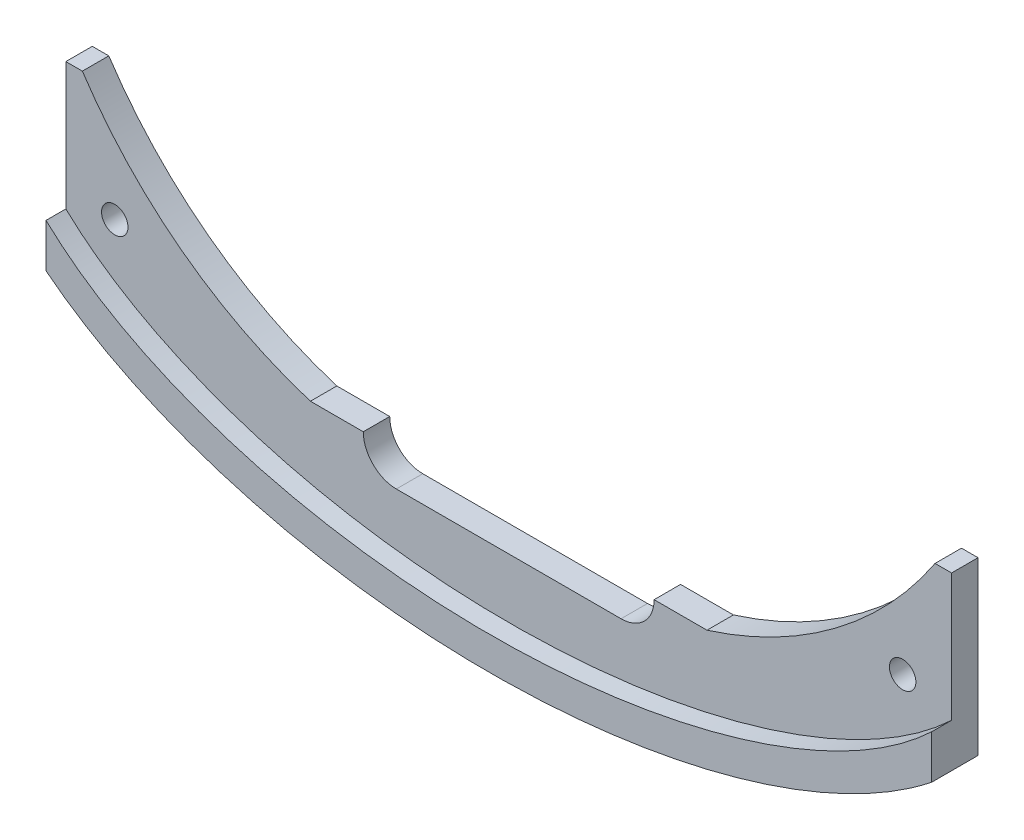
SolidWorks part; units mm, degrees
ref_plane "Alzado" through (0, 0, 0) normal (0, 0, 1) x (1, 0, 0)
ref_plane "Planta" through (0, 0, 0) normal (0, 1, 0) x (1, 0, 0)
ref_plane "Vista lateral" through (0, 0, 0) normal (1, 0, 0) x (0, 0, -1)
sketch "Croquis1" plane through (0, 0, 0) normal (0, 0, 1) x (1, 0, 0)
  line L0 (0, 14) -> (30, 14)
  line L3 (-76.5, 40) -> (-64.5, 40)
  line L5 (0, 14) -> (-30, 14)
  line L6 (0, 0) -> (0, 40) construction
  line L7 (64.5, 40) -> (76.5, 40)
  line L8 (-59.6, 23) -> (59.6, 23) construction
  circle A0 centre (7.25, 8) radius 2
  circle A1 centre (59.6, 23) radius 2
  circle A2 centre (-7.25, 8) radius 2
  circle A3 centre (-59.6, 23) radius 2
  arc A6 (-30, 14) -> (-64.5, 40) centre (-10.6545, 75.5595) cw
  arc A7 (30, 14) -> (64.5, 40) centre (10.6545, 75.5595) ccw
  ellipse E0 centre (0, 40) end of major axis (76.5, 40) minor radius 40 (-76.5, 40) -> (76.5, 40) ccw
  dimension "D3" = 4
  dimension "D5" = 4
  dimension "D10" = 8
  dimension "D2" = 153
  dimension "D4" = 30
  dimension "D6" = 119.2
  dimension "D7" = 15
  dimension "D8" = 40
  dimension "D9" = 12
  dimension "D11" = 14.5
  dimension "D12" = 14
extrude "Saliente-Extruir1" add sketch "Croquis1" along normal blind 4
ref_plane "Plano1" through (0, 0, -3) normal (0, 0, -1) x (-1, 0, 0)
sketch "Croquis2" plane through (0, 0, -3) normal (0, 0, -1) x (-1, 0, 0)
  line L3 (0, 0) -> (0, 33.4572) construction
  line L6 (64.5, 40) -> (76.5, 40) construction
  line L7 (-30, 14) -> (30, 14) construction
  line L8 (-76.5, 40) -> (-64.5, 40) construction
  line L9 (64.5, 40) -> (76.5, 40)
  line L10 (-30, 14) -> (30, 14)
  line L11 (-76.5, 40) -> (-64.5, 40)
  arc A8 (30, 14) -> (64.5, 40) centre (10.6545, 75.5595) ccw construction
  circle A10 centre (-59.6, 23) radius 2 construction
  circle A12 centre (7.25, 8) radius 2 construction
  circle A13 centre (-7.25, 8) radius 2 construction
  arc A14 (-64.5, 40) -> (-30, 14) centre (-10.6545, 75.5595) ccw construction
  arc A15 (30, 14) -> (64.5, 40) centre (10.6545, 75.5595) ccw
  circle A17 centre (-59.6, 23) radius 2
  circle A19 centre (7.25, 8) radius 2
  circle A20 centre (-7.25, 8) radius 2
  arc A21 (-64.5, 40) -> (-30, 14) centre (-10.6545, 75.5595) ccw
  circle A22 centre (59.6, 23) radius 2 construction
  circle A23 centre (59.6, 23) radius 2
  ellipse E0 centre (0, 40) end of major axis (-76.5, 40) minor radius 40 (-76.5, 40) -> (76.5, 40) ccw construction
  ellipse E1 centre (0, 40) end of major axis (-76.5, 40) minor radius 40 (-76.5, 40) -> (76.5, 40) ccw
extrude "Saliente-Extruir2" add sketch "Croquis2" along normal blind 4 separate body
ref_plane "Plano2" through (0, 0, 4) normal (0, 0, 1) x (1, 0, 0)
sketch "Croquis3" plane through (0, 0, 4) normal (0, 0, 1) x (1, 0, 0)
  line L2 (-81.5, 40) -> (-76.5, 40)
  line L3 (81.5, 40) -> (76.5, 40)
  ellipse E1 centre (0, 40) end of major axis (76.5, 40) minor radius 40 (-76.5, 40) -> (76.5, 40) ccw construction
  ellipse E2 centre (0, 40) end of major axis (76.5, 40) minor radius 40 (-76.5, 40) -> (76.5, 40) ccw
  spline S0 degree 1 poles (-81.5, 40) (81.5, 40) knots 0 0 1 1 construction
  spline S1 degree 3 poles (-81.5, 40) (-81.5, 36.7505) (-80.261, 30.281) (-73.3217, 18.4428) (-57.7398, 6.4288) (-31.0655, -2.8514) (0, -6.0743) (31.0655, -2.8514) (57.7398, 6.4288) (73.3217, 18.4428) (80.261, 30.281) (81.5, 36.7505) (81.5, 40) knots 3.141593 3.141593 3.141593 3.141593 3.337942 3.534292 3.926991 4.31969 4.712389 5.105088 5.497787 5.890486 6.086836 6.283185 6.283185 6.283185 6.283185
  dimension "D1" = 5
extrude "Saliente-Extruir3" add sketch "Croquis3" against normal up to surface (11 mm away) contours L3 E2 L2 S1 up to face at (5.25, 8, -7)
sketch "Croquis4" plane through (0, 0, 0) normal (0, 0, 1) x (1, 0, 0)
  line L0 (30, 14) -> (-30, 14) construction
  line L1 (30, 14) -> (-30, 14)
  line L2 (-39.8217, 18) -> (39.8217, 18)
  arc A0 (-64.5, 40) -> (-30, 14) centre (-10.6545, 75.5595) ccw construction
  arc A1 (30, 14) -> (64.5, 40) centre (10.6545, 75.5595) ccw construction
  arc A2 (-39.8217, 18) -> (-30, 14) centre (-10.6545, 75.5595) ccw
  arc A3 (30, 14) -> (39.8217, 18) centre (10.6545, 75.5595) ccw
  dimension "D1" = 4
extrude "Saliente-Extruir4" add sketch "Croquis4" along normal blind 4
sketch "Croquis5" plane through (0, 0, 4) normal (0, 0, 1) x (1, 0, 0)
  line L0 (39.8217, 18) -> (-39.8217, 18) construction
  line L1 (40.755, 18) -> (-40.755, 18)
  line L2 (40.755, 18) -> (40.755, 14)
  line L3 (40.755, 14) -> (-40.755, 14)
  line L4 (-40.755, 18) -> (-40.755, 14)
  point P6 (0, 14)
  dimension "D1" = 4
  dimension "D2" = 81.51
extrude "Saliente-Extruir5" add sketch "Croquis5" along normal blind 45 contours L2 L1 L4 L3
sketch "Croquis6" plane through (0, 14, 0) normal (0, -1, 0) x (-1, 0, 0)
  line L0 (13.075, -29) -> (-13.075, -29) construction
  line L1 (40.755, -4) -> (-40.755, -4) construction
  line L2 (0, -4) -> (0, -39) construction
  line L3 (35.826, -4) -> (35.826, -49) construction
  line L4 (-40.755, -4) -> (40.755, -4) construction
  line L5 (-40.755, -49) -> (40.755, -49) construction
  circle A0 centre (13.075, -29) radius 8.15
  circle A1 centre (-13.075, -29) radius 8.125
  circle A2 centre (35.826, -43.4034) radius 2.65
  circle A3 centre (35.826, -33.4034) radius 2.65
  circle A4 centre (-35.826, -33.4034) radius 2.65
  circle A5 centre (-35.826, -43.4034) radius 2.65
  point P18 (0, -29)
  dimension "D2" = 16.3
  dimension "D3" = 16.25
  dimension "D6" = 5.3
  dimension "D7" = 5.3
  dimension "D4" = 26.15
  dimension "D1" = 25
  dimension "D8" = 10
extrude "Cortar-Extruir1" cut sketch "Croquis6" against normal blind 25 contours A2 | A3 | A0 | A1 | A5 | A4
ref_plane "Plano4" through (0, -1, 0) normal (0, 1, 0) x (1, 0, 0)
sketch "Croquis7" plane through (0, -1, 0) normal (0, 1, 0) x (1, 0, 0)
  line L0 (0, -9.7855) -> (0, 13.9568) construction
  line L1 (-81.5, -4) -> (81.5, -4) construction
  line L2 (-55, -4) -> (-45, -4)
  line L3 (-55, -4) -> (-55, 7)
  line L4 (-55, 7) -> (-45, 7)
  line L5 (-45, -4) -> (-45, 7)
  line L6 (81.5, 7) -> (-81.5, 7) construction
  line L7 (55, 7) -> (45, 7)
  line L8 (55, -4) -> (55, 7)
  line L9 (55, -4) -> (45, -4)
  line L10 (45, -4) -> (45, 7)
  dimension "D1" = 10
  dimension "D2" = 55
extrude "Saliente-Extruir6" [suppressed] add sketch "Croquis7" along normal up to surface and the other way blind 6.08
sketch "Croquis16" [suppressed] plane through (0, -9.08, 0) normal (0, -1, 0) x (1, 0, 0)
  line L8 (-50, -6.5) -> (-50, 4.3) construction
  line L9 (-55, -1.1) -> (-45, -1.1) construction
  line L18 (50, 4.3) -> (50, -6.5) construction
  line L19 (45, -1.1) -> (55, -1.1) construction
  circle A0 centre (-50, -1.1) radius 4
  circle A1 centre (50, -1.1) radius 4
  dimension "D1" = 8
  dimension "D2" = 8
extrude "Cortar-Extruir6" [suppressed] cut sketch "Croquis16" against normal blind 16.3
sketch "Croquis17" plane through (0, 14, 0) normal (0, -1, 0) x (1, 0, 0)
  line L0 (-20.0239, 37.988) -> (-14.3005, 42.0182) construction
  line L1 (-20.5996, 38.8056) -> (-14.8763, 42.8359)
  line L2 (-19.4481, 37.1703) -> (-13.7248, 41.2006)
  line L3 (14.2242, 42.0182) -> (19.9475, 37.988) construction
  line L4 (14.7999, 42.8359) -> (20.5233, 38.8056)
  line L5 (13.6484, 41.2006) -> (19.3718, 37.1703)
  line L7 (-0.0382, 31.8728) -> (-0.0382, 6.8728) construction
  line L8 (-14.3005, 42.0182) -> (14.2242, 42.0182) construction
  line L9 (-20.0239, 37.988) -> (19.9475, 37.988) construction
  arc A0 (-20.5996, 38.8056) -> (-19.4481, 37.1703) centre (-20.0239, 37.988) ccw
  arc A1 (-13.7248, 41.2006) -> (-14.8763, 42.8359) centre (-14.3005, 42.0182) ccw
  arc A2 (14.7999, 42.8359) -> (13.6484, 41.2006) centre (14.2242, 42.0182) ccw
  arc A3 (19.3718, 37.1703) -> (20.5233, 38.8056) centre (19.9475, 37.988) ccw
  arc A4 (-20.8514, 31.4391) -> (-21.2225, 29.203) centre (-13.075, 29) ccw
  arc A6 (-10.8066, 17.5553) -> (11.1701, 17.5553) centre (0.1818, 45.4654) ccw
  arc A7 (-11.1729, 16.6248) -> (11.5364, 16.6248) centre (0.1818, 45.4654) ccw
  arc A8 (-10.8066, 17.5553) -> (-11.1729, 16.6248) centre (-10.9898, 17.09) ccw
  arc A9 (11.5364, 16.6248) -> (11.1701, 17.5553) centre (11.3533, 17.09) ccw
  circle A10 centre (-13.075, 29) radius 8.15 construction
  arc A13 (20.7751, 31.4391) -> (21.1461, 29.203) centre (12.9987, 29) cw
  ellipse E0 centre (-0.0382, 20.6274) end of major axis (3.8018, 20.6274) minor radius 1.3066
  spline S0 degree 2 poles (-20.8514, 31.4391) (-23.6077, 31.2523) (-25.4765, 33.8858) knots 0 0 0 1 1 1
  spline S1 degree 3 poles (-25.4765, 33.8858) (-24.9367, 29.7669) (-23.9591, 29.7982) (-21.2225, 29.203) knots 0 0 0 0 0.707855 0.707855 0.707855 0.707855
  spline S2 degree 3 poles (25.4002, 33.8858) (24.8603, 29.7669) (23.8827, 29.7982) (21.1461, 29.203) knots 0 0 0 0 0.707855 0.707855 0.707855 0.707855
  spline S3 degree 2 poles (20.7751, 31.4391) (23.5313, 31.2523) (25.4002, 33.8858) knots 0 0 0 1 1 1
  point P2 (-17.1622, 40.0031)
  point P7 (17.0859, 40.0031)
  point P54 (-0.0382, 37.988)
  dimension "D2" = 1
  dimension "D1" = 7
extrude "Saliente-Extruir9" add sketch "Croquis17" along normal blind 2
sketch "Croquis18" [suppressed] plane through (0, 0, -6.6) normal (0, 0, -1) x (-1, 0, 0)
  line L0 (0, 12) -> (0, -15.2947) construction
  line L1 (30, 12) -> (-30, 12) construction
  line L2 (50, 2.42) -> (50, -5.58) construction
  line L3 (51.5, 2.42) -> (51.5, -5.58)
  line L4 (48.5, 2.42) -> (48.5, -5.58)
  line L5 (55, -9.08) -> (55, 5.7348) construction
  line L6 (45, -9.08) -> (45, 1.7946) construction
  line L7 (-50, 2.42) -> (-50, -5.58) construction
  line L8 (-51.5, 2.42) -> (-51.5, -5.58)
  line L9 (-48.5, 2.42) -> (-48.5, -5.58)
  line L10 (45, -9.08) -> (55, -9.08) construction
  arc A0 (51.5, 2.42) -> (48.5, 2.42) centre (50, 2.42) ccw
  arc A1 (48.5, -5.58) -> (51.5, -5.58) centre (50, -5.58) ccw
  arc A2 (-51.5, 2.42) -> (-48.5, 2.42) centre (-50, 2.42) cw
  arc A3 (-48.5, -5.58) -> (-51.5, -5.58) centre (-50, -5.58) cw
  point P7 (50, -1.58)
  point P18 (-50, -1.58)
  dimension "D2" = 1.5
  dimension "D1" = 8
  dimension "D3" = 3.5
extrude "Cortar-Extruir7" [suppressed] cut sketch "Croquis18" against normal through all
sketch "Croquis19" [suppressed] plane through (0, 0, -3) normal (0, 0, 1) x (1, 0, 0)
  line L0 (0, 0) -> (0, 34.2296) construction
  line L2 (-64.5, 40) -> (-81.5, 40) construction
  circle A0 centre (0, -2.5) radius 0.75
  circle A1 centre (-79, 36.5) radius 0.75
  circle A2 centre (79, 36.5) radius 0.75
  dimension "D1" = 1.5
  dimension "D2" = 1.5
  dimension "D4" = 2.5
  dimension "D3" = 2.5
  dimension "D5" = 3.5
sketch "Croquis20" plane through (0, 0, 0) normal (1, 0, 0) x (0, 0, -1)
  line L0 (0, 40) -> (0, -5)
  line L1 (-4, -5) -> (7, -5) construction
  line L2 (0, -5) -> (-49.6594, -5)
  line L3 (-49.6594, -5) -> (-49.6594, 40)
  line L4 (-49.6594, 40) -> (0, 40)
extrude "Cortar-Extruir9" cut sketch "Croquis20" against normal through all both and the other way through all
sketch "Croquis21" plane through (0, 0, -7) normal (0, 0, -1) x (-1, 0, 0)
  circle A0 centre (-7.25, 8) radius 2 construction
  circle A1 centre (7.25, 8) radius 2 construction
  circle A2 centre (-7.25, 8) radius 2
  circle A3 centre (7.25, 8) radius 2
extrude "Saliente-Extruir11" add sketch "Croquis21" against normal up to surface (4 mm away) up to face at (0, 23.6757, -3)
sketch "Croquis22" plane through (0, 0, -7) normal (0, 0, -1) x (-1, 0, 0)
  line L0 (67, 40) -> (67, 14.0793)
  line L2 (-67, 40) -> (-67, 14.0793)
  line L4 (67, 14.0793) -> (95.2028, 14.0793)
  line L5 (67, 14.0793) -> (67, 40)
  line L6 (67, 40) -> (95.2028, 40)
  line L7 (95.2028, 14.0793) -> (95.2028, 40)
  line L8 (-67, 14.0793) -> (-97.8279, 14.0793)
  line L9 (-67, 14.0793) -> (-67, 40)
  line L10 (-67, 40) -> (-97.8279, 40)
  line L11 (-97.8279, 14.0793) -> (-97.8279, 40)
  spline S1 degree 3 poles (81.5, 40) (81.5, 36.7505) (80.261, 30.281) (73.3217, 18.4428) (57.7398, 6.4288) (31.0655, -2.8514) (0, -6.0743) (-31.0655, -2.8514) (-57.7398, 6.4288) (-73.3217, 18.4428) (-80.261, 30.281) (-81.5, 36.7505) (-81.5, 40) knots 3.141593 3.141593 3.141593 3.141593 3.337942 3.534292 3.926991 4.31969 4.712389 5.105088 5.497787 5.890486 6.086836 6.283185 6.283185 6.283185 6.283185 construction
  spline M3 degree 3 poles (-81.5, 40) (-81.5, 36.7505) (-80.261, 30.281) (-73.3217, 18.4428) (-57.7398, 6.4288) (-31.0655, -2.8514) (0, -6.0743) (31.0655, -2.8514) (57.7398, 6.4288) (73.3217, 18.4428) (80.261, 30.281) (81.5, 36.7505) (81.5, 40) knots 3.141593 3.141593 3.141593 3.141593 3.337942 3.534292 3.926991 4.31969 4.712389 5.105088 5.497787 5.890486 6.086836 6.283185 6.283185 6.283185 6.283185
  line M4 (81.5, 40) -> (64.5, 40)
  line M8 (-64.5, 40) -> (-81.5, 40)
  dimension "D1" = 134
  dimension "D2" = 67
extrude "Cortar-Extruir10" cut sketch "Croquis22" against normal blind 10 contours L4 L7 L6 M3 | L2 M8 M3 | L11 L8 L10 M3 | L0 M4 M3 region at (-72.8551, 30.1323, -7) region at (86.9254, 25.58, -7) region at (72.8551, 30.1323, -7) region at (-85.5511, 25.3709, -7)
sketch "Croquis23" plane through (0, 0, 0) normal (1, 0, 0) x (0, 0, -1)
  line L0 (7, 14) -> (7, -6.3364)
  line L1 (7, 14) -> (9, 14)
  line L2 (9, 14) -> (9, 13)
  line L3 (9, 13) -> (8, 13)
  line L4 (8, 13) -> (8, 8)
  line L5 (8, 8) -> (11, 8)
  line L6 (11, 8) -> (11, 10)
  line L7 (11, 10) -> (13, 10)
  line L8 (13, 10) -> (13, 6)
  line L9 (13, 6) -> (7, 6)
  line L10 (7, 21) -> (7, 25) construction
  dimension "D1" = 2
  dimension "D2" = 1
  dimension "D3" = 5
  dimension "D4" = 3
  dimension "D5" = 2
  dimension "D6" = 2
  dimension "D7" = 2
  dimension "D8" = 1
extrude "Saliente-Extruir12" [suppressed] add sketch "Croquis23" along normal blind 13 and the other way blind 13 contours L9 L8 L7 L6 L5 L4 L3 L2 L1 L0
sketch "Croquis24" plane through (0, 0, -7) normal (0, 0, -1) x (-1, 0, 0)
  line L0 (30, 14) -> (-30, 14) construction
  line L1 (22, 14) -> (-22, 14)
  line L2 (22, 14) -> (22, 9)
  line L3 (22, 9) -> (-22, 9)
  line L4 (-22, 14) -> (-22, 9)
  point P6 (0, 9)
  dimension "D1" = 44
  dimension "D2" = 5
extrude "Saliente-Extruir10" [suppressed] add sketch "Croquis19" along normal blind 6
extrude "Cortar-Extruir11" cut sketch "Croquis24" against normal blind 10
fillet "Redondeo1" radius 5 2 edges at (-22, 9, -5) (22, 9, -5)
